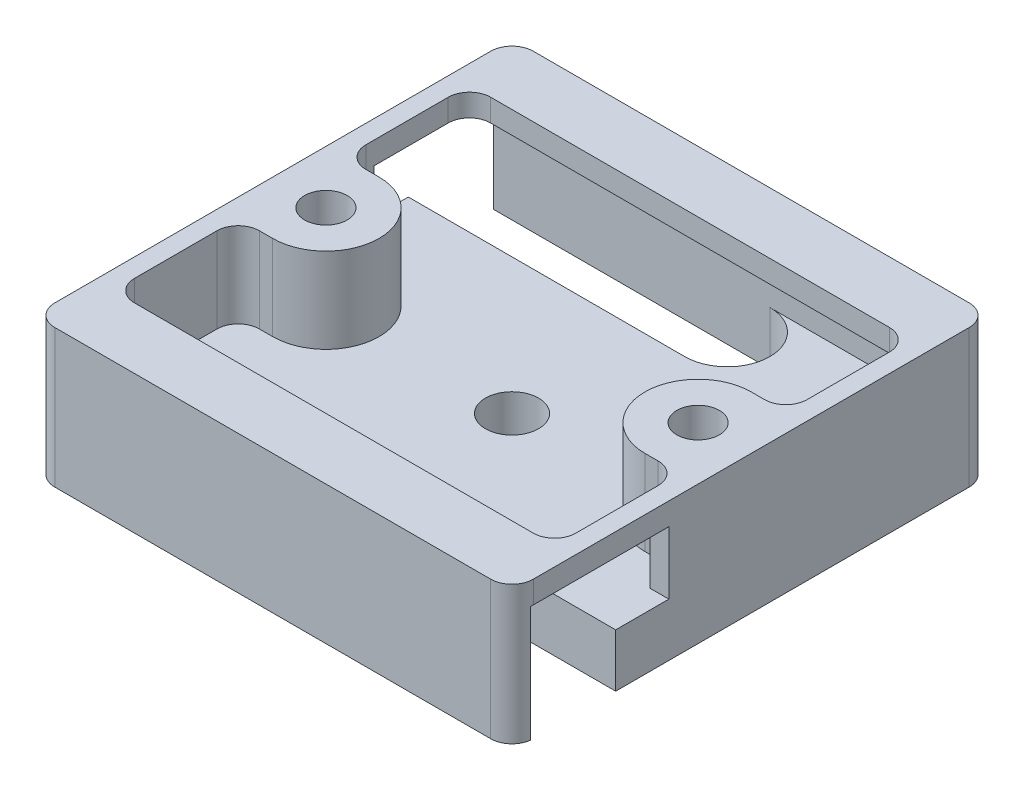
SolidWorks part; units mm, degrees
ref_plane "Alzado" through (0, 0, 0) normal (0, 0, 1) x (1, 0, 0)
ref_plane "Planta" through (0, 0, 0) normal (0, 1, 0) x (1, 0, 0)
ref_plane "Vista lateral" through (0, 0, 0) normal (1, 0, 0) x (0, 0, -1)
sketch "Croquis1" plane through (0, 0, 0) normal (0, 1, 0) x (1, 0, 0)
  line L0 (22.5, -16.75) -> (-3.5, -16.75) construction
  line L1 (-18.5, -18.5) -> (18.5, -18.5) construction
  line L2 (-18.5, -18.5) -> (-18.5, 18.5) construction
  line L3 (-18.5, 18.5) -> (18.5, 18.5) construction
  line L4 (18.5, -18.5) -> (18.5, 18.5) construction
  line L5 (-18.5, -18.5) -> (18.5, 18.5) construction
  line L6 (-18.5, 18.5) -> (18.5, -18.5) construction
  line L7 (-20.75, -20.75) -> (20.75, -20.75) construction
  line L8 (-20.75, -20.75) -> (-20.75, 20.75) construction
  line L9 (-20.75, 20.75) -> (20.75, 20.75) construction
  line L10 (20.75, -20.75) -> (20.75, 20.75) construction
  line L11 (-20.75, -20.75) -> (20.75, 20.75) construction
  line L12 (-20.75, 20.75) -> (20.75, -20.75) construction
  line L13 (-22.5, -22.5) -> (22.5, -22.5)
  line L14 (-22.5, -22.5) -> (-22.5, 22.5)
  line L15 (-22.5, 22.5) -> (22.5, 22.5)
  line L16 (22.5, -22.5) -> (22.5, 22.5)
  line L17 (-22.5, -22.5) -> (22.5, 22.5) construction
  line L18 (-22.5, 22.5) -> (22.5, -22.5) construction
  line L19 (22.5, -20.75) -> (-3.5, -20.75)
  line L20 (22.5, -12.75) -> (-3.5, -12.75)
  line L21 (-7.5, 0) -> (-7.5, -16.75) construction
  line L22 (-22.5, 16.75) -> (3.5, 16.75) construction
  line L23 (-22.5, 20.75) -> (3.5, 20.75)
  line L24 (-22.5, 12.75) -> (3.5, 12.75)
  line L25 (7.5, 16.75) -> (7.5, 0) construction
  line L26 (-3.5, -20.75) -> (-20.75, -20.75)
  line L27 (-20.75, -20.75) -> (-20.75, 7.75)
  line L28 (3.5, 20.75) -> (20.75, 20.75)
  line L29 (20.75, 20.75) -> (20.75, -7.75)
  line L30 (-20.75, 7.75) -> (-22.5, 7.75)
  line L31 (20.75, -7.75) -> (22.5, -7.75)
  circle A0 centre (0, 0) radius 7.5 construction
  arc A1 (22.5, -20.75) -> (22.5, -12.75) centre (22.5, -16.75) ccw
  arc A2 (-3.5, -12.75) -> (-3.5, -20.75) centre (-3.5, -16.75) ccw
  arc A3 (-22.5, 20.75) -> (-22.5, 12.75) centre (-22.5, 16.75) ccw
  arc A4 (3.5, 12.75) -> (3.5, 20.75) centre (3.5, 16.75) ccw
  circle A5 centre (0, 0) radius 2.5
  point P0 (0, 0)
  point P5 (0, 0)
  point P19 (9.5, -16.75)
  point P28 (-9.5, 16.75)
  dimension "D7" = 4
  dimension "D8" = 15
  dimension "D12" = 5
  dimension "D1" = 37
  dimension "D2" = 37
  dimension "D3" = 2.25
  dimension "D4" = 2.25
  dimension "D5" = 45
  dimension "D6" = 45
  dimension "D9" = 1.75
  dimension "D10" = 5
  dimension "D11" = 5
extrude "Saliente-Extruir1" add sketch "Croquis1" against normal blind 5 contours L27 L30 L14 L13 L16 L19 L26 | A4 L24 L14 L30 L27 L26 A2 L20 L16 L31 L29 L28 A0 | L29 L31 L16 L15 L14 L23 L28 region at (-21.9578, 0, 7.375) region at (-21.8879, 0, -10.25) region at (-21.9578, 0, -21.625)
extrude "Saliente-Extruir2" add sketch "Croquis1<3>" along normal blind 6 contours L27 L30 L14 L13 L16 L19 L26 | L29 L31 L16 L15 L14 L23 L28 region at (-21.9578, 0, 7.375) region at (-21.9578, 0, -21.625)
sketch "Croquis1<3>" plane through (0, 0, 0) normal (0, 1, 0) x (1, 0, 0) same geometry as "Croquis1"
sketch "Croquis2" plane through (0, 6, 0) normal (0, 1, 0) x (1, 0, 0)
  line L12 (-22.5, 22.5) -> (22.5, 22.5)
  line L33 (22.5, 22.5) -> (22.5, -22.5)
  line L34 (22.5, -22.5) -> (-22.5, -22.5)
  line L35 (-22.5, -22.5) -> (-22.5, 22.5)
  line L37 (-20.75, -20.75) -> (-20.75, 7.75) construction
  line L38 (-20.75, -22.5) -> (-20.75, 22.5)
  line L40 (20.75, 22.5) -> (20.75, -22.5)
  line L41 (20.75, 20.75) -> (20.75, -7.75) construction
  line L42 (-20.75, 16.75) -> (20.75, 16.75)
  line L43 (20.75, -16.75) -> (-20.75, -16.75)
  line L44 (22.5, -20.75) -> (-20.75, -20.75) construction
  line L45 (-22.5, 20.75) -> (20.75, 20.75) construction
  line M9 (-20.75, -20.75) -> (-20.75, 7.75)
  line M10 (-20.75, 7.75) -> (-22.5, 7.75)
  line M11 (-22.5, 7.75) -> (-22.5, -22.5)
  line M12 (-22.5, -22.5) -> (22.5, -22.5)
  line M13 (22.5, -22.5) -> (22.5, -20.75)
  line M14 (22.5, -20.75) -> (-20.75, -20.75)
  dimension "D1" = 4
  dimension "D2" = 4
extrude "Saliente-Extruir5" add sketch "Croquis2" along normal blind 2 and the other way blind 0.1 contours L38 L42 L40 L12 | L38 L12 L35 M10 | L40 L43 M9 M14 | L40 L38 L34 M14 | L38 M12 M9 M10 M11 | L12 L40 L33 M14 | L40 M14 M12 M13 region at (-21.625, 6, -15.125) region at (0, 6, -19.625) region at (-21.625, 6, 7.375) region at (21.625, 6, -0.875) region at (0, 6, 21.625) region at (0, 6, 18.75) region at (21.625, 6, 21.625)
sketch "Croquis3" plane through (0, 8, 0) normal (0, 1, 0) x (1, 0, 0)
  line L0 (-22.5, -22.5) -> (-22.5, 22.5) construction
  line L1 (-22.5, -5) -> (-17.5, -5)
  line L2 (-22.5, -5) -> (-22.5, 5)
  line L3 (-22.5, 5) -> (-17.5, 5)
  line L4 (-17.5, -5) -> (-17.5, 5)
  line L5 (0, 22.5) -> (0, -22.5) construction
  line L6 (-22.5, 22.5) -> (22.5, 22.5) construction
  line L7 (-22.5, -22.5) -> (22.5, -22.5) construction
  line L8 (-22.5, 0) -> (20.75, 0) construction
  line L9 (20.75, 20.75) -> (20.75, -7.75) construction
  arc A0 (-17.5, 5) -> (-17.5, -5) centre (-17.5, 0) cw
  circle A1 centre (-17.5, 0) radius 2
  point P19 (-12.5, 0)
  line M7 (-20.75, -16.75) -> (-20.75, 16.75)
  dimension "D3" = 4
  dimension "D2" = 5
  dimension "D1" = 10
extrude "Saliente-Extruir6" add sketch "Croquis3" against normal up to surface (8 mm away) contours A1 L4 L3 L1 M7 | A1 L4 A0 | L4 A1 | L4 A1 region at (-20.6449, 8, 0) region at (-15.1354, 8, 0) region at (-18.3488, 8, 0) region at (-16.6512, 8, 0) up to face at (0, 0, 2.5)
extrude "Cortar-Extruir1" cut sketch "Croquis3<3>" against normal up to next contours L4 A1 | L4 A1 region at (-18.3488, 8, 0) region at (-16.6512, 8, 0)
sketch "Croquis3<3>" plane through (0, 8, 0) normal (0, 1, 0) x (1, 0, 0) same geometry as "Croquis3"
mirror "Simetría1" about plane through (0, 0, 0) normal (1, 0, 0) of "Saliente-Extruir6", "Cortar-Extruir1"
sketch "Croquis4" plane through (0, -5, 0) normal (0, -1, 0) x (1, 0, 0)
  circle A0 centre (17.5, 0) radius 2 construction
  circle A1 centre (-17.5, 0) radius 2 construction
  circle A2 centre (17.5, 0) radius 2
  circle A3 centre (-17.5, 0) radius 2
  circle A4 centre (-17.5, 0) radius 3.5
  circle A5 centre (17.5, 0) radius 3.5
  dimension "D1" = 1.5
  dimension "D2" = 1.5
  dimension "D4" = 7
  dimension "D5" = 4
  dimension "D3" = 35
extrude "Cortar-Extruir2" cut sketch "Croquis4" against normal blind 3
fillet "Redondeo1" radius 2 8 edges at (-20.75, 4, -5) (-20.75, 4, 5) (20.75, 4, 5) (20.75, 4, -5) (20.75, 6.95, -16.75) (-20.75, 6.95, 16.75) (-20.75, 6.95, -16.75) (20.75, 6.95, 16.75)
fillet "Redondeo2" radius 2 6 edges at (-22.5, 1.5, -22.5) (22.5, 1.5, -22.5) (-22.5, 1.5, 22.5) (22.5, 1.5, 22.5) (20.75, 2.95, -20.75) (-20.75, 2.95, 20.75)
equation "\"D2@Croquis1\"=\"D1@Croquis1\""
equation "\"D6@Croquis1\"=\"D5@Croquis1\""
